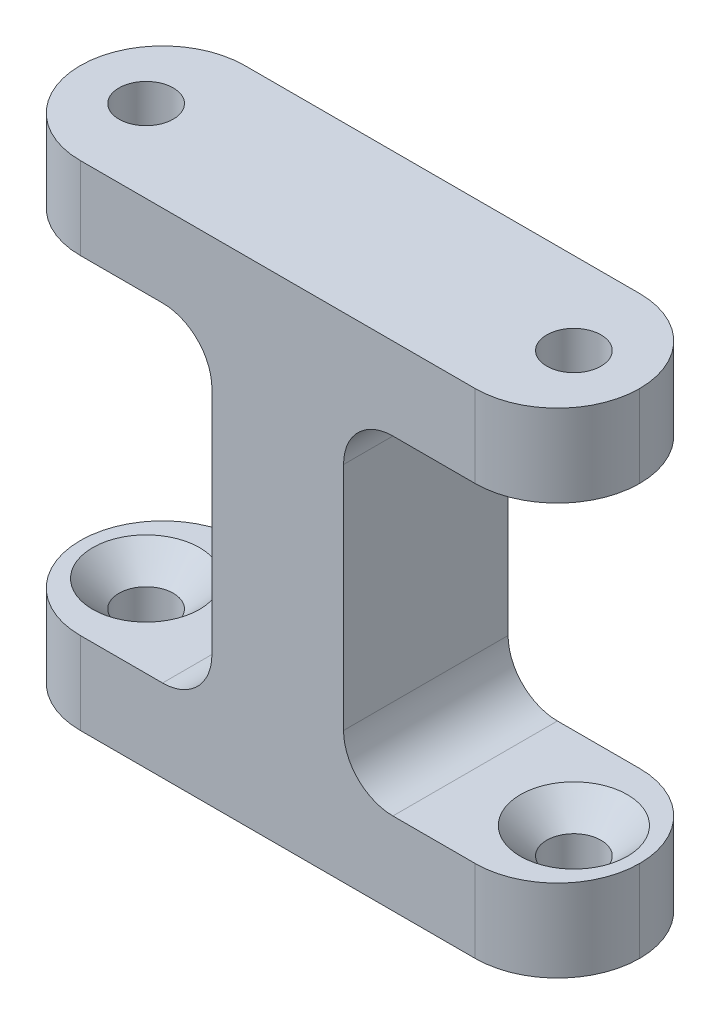
SolidWorks part; units mm, degrees
material "PLA Black"
ref_plane "Front Plane" through (0, 0, 0) normal (0, 0, 1) x (1, 0, 0)
ref_plane "Top Plane" through (0, 0, 0) normal (0, 1, 0) x (1, 0, 0)
ref_plane "Right Plane" through (0, 0, 0) normal (1, 0, 0) x (0, 0, -1)
sketch "Sketch1" plane through (0, 0, 0) normal (0, 0, 1) x (1, 0, 0)
  line L0 (0, 0) -> (0, 5)
  line L1 (0, 5) -> (-13, 5)
  line L2 (-13, 5) -> (-13, 25)
  line L3 (-13, 25) -> (0, 25)
  line L4 (0, 25) -> (0, 30)
  line L5 (0, 30) -> (-34, 30)
  line L6 (-34, 30) -> (-34, 25)
  line L7 (-34, 25) -> (-21, 25)
  line L8 (-21, 25) -> (-21, 5)
  line L9 (-21, 5) -> (-34, 5)
  line L10 (-34, 5) -> (-34, 0)
  line L11 (-34, 0) -> (0, 0)
  line L12 (-17, 30) -> (-17, 35.187) construction
  dimension "D1" = 34
  dimension "D2" = 30
  dimension "D3" = 5
  dimension "D4" = 5
  dimension "D5" = 8
  dimension "D6" = 4
extrude "Boss-Extrude1" add sketch "Sketch1" along normal blind 10
sketch "Sketch2" plane through (0, 30, 0) normal (0, 1, 0) x (1, 0, 0)
  line L0 (0, 0) -> (-34, 0) construction
  line L2 (-17, 0) -> (-17, 9.2257) construction
  circle A0 centre (-30, -5) radius 1.65
  circle A1 centre (-4, -5) radius 1.65
  dimension "D1" = 3.3
  dimension "D2" = 3.3
  dimension "D3" = 26
  dimension "D4" = 5
  dimension "D5" = 13
extrude "Cut-Extrude1" cut sketch "Sketch2" against normal through all both and the other way through all
chamfer "Chamfer1" distance 1.6 angle 45 2 edges at (-28.35, 5, 5) (-2.35, 5, 5)
fillet "Fillet1" radius 3 4 edges at (-13, 25, 5) (-21, 25, 5) (-21, 5, 5) (-13, 5, 5)
fillet "Fillet3" radius 5 8 edges at (-34, 2.5, 0) (-34, 2.5, 10) (0, 2.5, 10) (0, 2.5, 0) (0, 27.5, 0) (0, 27.5, 10) (-34, 27.5, 0) (-34, 27.5, 10)
